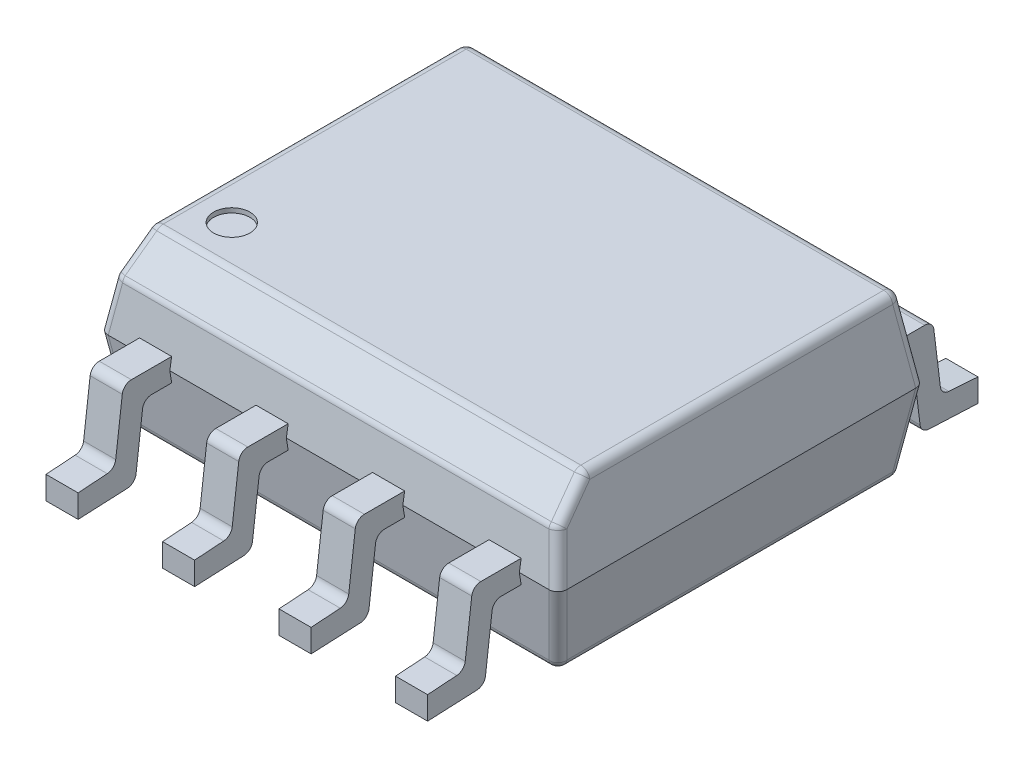
SolidWorks part; units mm, degrees
ref_plane "Alzado" through (0, 0, 0) normal (0, 0, 1) x (1, 0, 0)
ref_plane "Planta" through (0, 0, 0) normal (0, 1, 0) x (1, 0, 0)
ref_plane "Vista lateral" through (0, 0, 0) normal (1, 0, 0) x (0, 0, -1)
sketch "Croquis1" plane through (0, 0, 0) normal (0, 1, 0) x (1, 0, 0)
  line L1 (2.5, 2) -> (-2.5, 2)
  line L2 (2.5, 2) -> (2.5, -2)
  line L3 (2.5, -2) -> (-2.5, -2)
  line L4 (-2.5, 2) -> (-2.5, -2)
  line L5 (2.5, 2) -> (-2.5, -2) construction
  line L6 (2.5, -2) -> (-2.5, 2) construction
  point P0 (0, 0)
  dimension "D1" = 4
  dimension "D2" = 5
extrude "Saliente-Extruir1" add sketch "Croquis1" along normal blind 1.75
sketch "Croquis2" plane through (0, 0, 2) normal (0, 0, 1) x (1, 0, 0)
  line L0 (-2.5, 0.875) -> (2.5, 0.875) construction
  line L3 (-2.5, 0.875) -> (-2.3614, 1.75)
  line L4 (-2.5, 0.875) -> (-2.3614, 0)
  line L5 (2.5, 0.875) -> (2.3614, 0)
  line L6 (-2.5, 0) -> (2.5, 0)
  line L7 (2.5, 0) -> (2.5, 1.75)
  line L8 (2.5, 1.75) -> (-2.5, 1.75)
  line L9 (-2.5, 1.75) -> (-2.5, 0)
  line L10 (-2.5, 0) -> (2.5, 0)
  line L11 (2.5, 0) -> (2.5, 1.75)
  line L12 (2.5, 1.75) -> (-2.5, 1.75)
  line L13 (-2.5, 1.75) -> (-2.5, 0)
  line L14 (2.3614, 1.75) -> (2.5, 0.875)
  line L15 (-2.5, 1.75) -> (-2.3614, 1.75)
  line L16 (-2.5, 1.75) -> (-2.5, 0.875)
  line M6 (-2.5, 0) -> (2.5, 0)
  line M7 (2.5, 0) -> (2.5, 1.75)
  line M8 (2.5, 1.75) -> (-2.5, 1.75)
  line M9 (-2.5, 1.75) -> (-2.5, 0)
  dimension "D2" = 5
  dimension "D3" = 0.875
  dimension "D4" = 9
  dimension "D5" = 9
  dimension "D6" = 9
  dimension "D7" = 9
  dimension "D1" = 0
sketch "Croquis3" plane through (0, 0, 2) normal (0, 0, 1) x (1, 0, 0)
extrude "Cortar-Extruir1" cut sketch "Croquis2" against normal through all contours L3 M9 M8 | L4 M9 M6 | L5 M7 M6 | L14 M8 M7 region at (-2.4538, 1.4583, 2) region at (-2.4538, 0.2917, 2) region at (2.4538, 1.4583, 2) region at (2.4538, 0.2917, 2)
sketch "Croquis5" plane through (0, 0, 0) normal (1, 0, 0) x (0, 0, -1)
  line L0 (2, 0.875) -> (-2, 0.875) construction
  line L1 (2, 0) -> (-2, 0)
  line L2 (2, 0) -> (2, 1.75)
  line L3 (2, 1.75) -> (-2, 1.75)
  line L4 (-2, 0) -> (-2, 1.75)
  line L5 (2, 0) -> (-2, 1.75) construction
  line L6 (2, 1.75) -> (-2, 0) construction
  line L7 (-2, 0.875) -> (-1.8614, 1.75)
  line L8 (2, 0.875) -> (1.8614, 1.75)
  line L9 (2, 0.875) -> (1.8614, 0)
  line L10 (-2, 0.875) -> (-1.8614, 0)
  point P0 (0, 0.875)
  dimension "D1" = 9
  dimension "D2" = 9
  dimension "D3" = 9
  dimension "D4" = 9
extrude "Cortar-Extruir3" cut sketch "Croquis5" against normal mid plane 5 contours L4 L7 L3 | L8 L2 L3 | L2 L9 L1 | L10 L4 L1 region at (0, 0.2917, -1.9538) region at (0, 1.4583, -1.9538) region at (0, 0.2917, 1.9538) region at (0, 1.4583, 1.9538)
fillet "Redondeo1" radius 0.1 4 edges at (0, 1.75, -1.8614) (0, 1.75, 1.8614) (2.3614, 1.75, 0) (-2.3614, 1.75, 0)
fillet "Redondeo2" radius 0.1 4 edges at (2.3614, 0, 0) (0, 0, -1.8614) (-2.3614, 0, 0) (0, 0, 1.8614)
fillet "Redondeo3" radius 0.1 16 edges at (2.341, 0.024, -1.841) (2.341, 1.726, -1.841) (2.341, 1.726, 1.841) (2.341, 0.024, 1.841) (-2.341, 0.024, 1.841) (-2.341, 1.726, 1.841) (-2.341, 0.024, -1.841) (-2.341, 1.726, -1.841) (2.4374, 0.4797, -1.9374) (2.4374, 1.2703, -1.9374) (2.4374, 1.2703, 1.9374) (2.4374, 0.4797, 1.9374) (-2.4374, 0.4797, 1.9374) (-2.4374, 1.2703, 1.9374) (-2.4374, 0.4797, -1.9374) (-2.4374, 1.2703, -1.9374)
sketch "Croquis6" plane through (0, 0, 0) normal (1, 0, 0) x (0, 0, -1)
  line L0 (1.9012, 0.875) -> (-1.9012, 0.875) construction
  line L1 (2, 0) -> (-2, 0)
  line L2 (2, 0) -> (2, 1.75)
  line L3 (2, 1.75) -> (-2, 1.75)
  line L4 (-2, 0) -> (-2, 1.75)
  line L5 (2, 0) -> (-2, 1.75) construction
  line L6 (2, 1.75) -> (-2, 0) construction
  line L7 (-1.9171, 1.4) -> (-1.5671, 1.75)
  line L8 (-2, 1.75) -> (-1.5671, 1.75)
  line L9 (-1.9171, 1.75) -> (-1.9171, 1.4)
  line L10 (-1.9171, 1.75) -> (-1.5671, 1.75)
  point P0 (0, 0.875)
  dimension "D1" = 1.75
  dimension "D2" = 4
  dimension "D3" = 45
  dimension "D4" = 0.35
extrude "Cortar-Extruir4" cut sketch "Croquis6" against normal mid plane 5 contours L3 L9 L7 region at (0, 1.6333, 1.8005)
fillet "Redondeo4" radius 0.1 8 edges at (2.341, 1.726, 1.5911) (0, 1.75, 1.5671) (-2.341, 1.726, 1.5911) (-2.3865, 1.5917, 1.7255) (-2.3826, 1.4345, 1.8826) (0, 1.4003, 1.9168) (2.3826, 1.4345, 1.8826) (2.3865, 1.5917, 1.7255)
sketch "Croquis7" plane through (0, 0, 0) normal (1, 0, 0) x (0, 0, -1)
  line L0 (1.9012, 0.875) -> (-1.9012, 0.875) construction
  line L5 (1.9012, 1) -> (2.5079, 1)
  line L6 (2.5079, 1) -> (2.6, 0.25)
  line L7 (-2.6, 0.25) -> (-3, 0.222)
  line L8 (-2.5079, 1) -> (-2.6, 0.25)
  line L9 (-1.9012, 0.75) -> (-2.2867, 0.75)
  line L11 (-1.9012, 1) -> (-2.5079, 1)
  line L13 (-2.2361, 1.1624) -> (-2.412, -0.2704) construction
  line L14 (-2.4842, 1.1929) -> (-2.6602, -0.24) construction
  line L19 (-3, 0.222) -> (-3, -0.0286)
  line L20 (-1.9012, 1) -> (-1.9012, 0.75)
  line L21 (-2.2867, 0.75) -> (-2.3788, 0)
  line L22 (0, 2.0779) -> (0, -0.2618) construction
  line L23 (-3, -0.0286) -> (-2.3788, 0)
  line L24 (2.6, 0.25) -> (3, 0.222)
  line L25 (3, 0.222) -> (3, -0.0286)
  line L26 (3, -0.0286) -> (2.3788, 0)
  line L27 (2.2867, 0.75) -> (2.3788, 0)
  line L28 (1.9012, 0.75) -> (2.2867, 0.75)
  line L29 (1.9012, 1) -> (1.9012, 0.75)
  point P0 (0, 0.875)
  point P1 (0, 0)
  point P2 (0, 0)
extrude "Saliente-Extruir2" add sketch "Croquis7" along normal mid plane 0.35 from offset 1.905 separate body
fillet "Redondeo7" radius 0.1 4 edges at (1.905, 0, 2.3788) (1.905, 0.25, 2.6) (1.905, 0.75, 2.2867) (1.905, 1, 2.5079)
fillet "Redondeo8" radius 0.1 4 edges at (1.905, 0.25, -2.6) (1.905, 0, -2.3788) (1.905, 0.75, -2.2867) (1.905, 1, -2.5079)
pattern_linear "MatrizL2" count 4 spacing 1.27 along (-1, 0, 0) of bodies 107 106
sketch "Croquis8" plane through (0, 1.75, 0) normal (0, 1, 0) x (1, 0, 0)
  circle A1 centre (-1.9167, -1.1381) radius 0.1979
extrude "Cortar-Extruir5" cut sketch "Croquis8" against normal blind 0.05 contours A1
